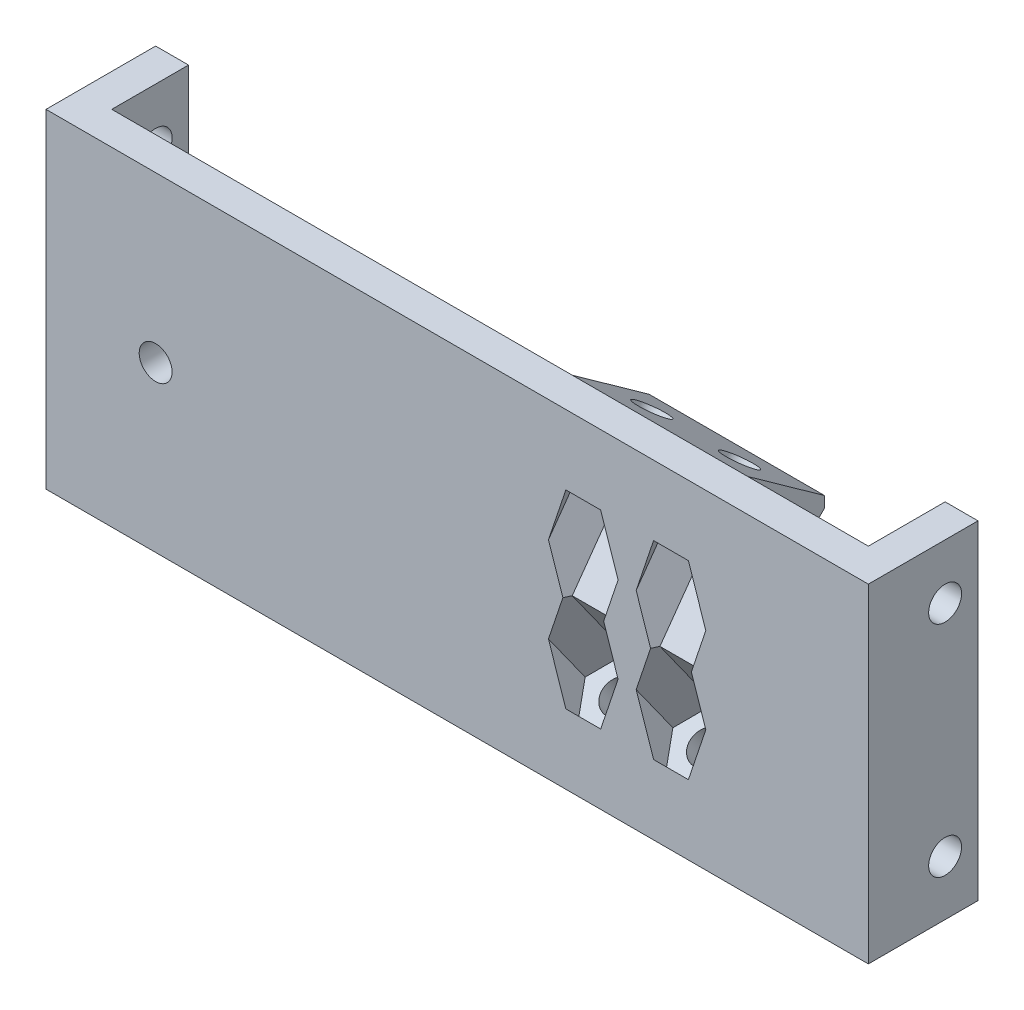
SolidWorks part; units mm, degrees
ref_plane "Front Plane" through (0, 0, 0) normal (0, 0, 1) x (1, 0, 0)
ref_plane "Top Plane" through (0, 0, 0) normal (0, 1, 0) x (1, 0, 0)
ref_plane "Right Plane" through (0, 0, 0) normal (1, 0, 0) x (0, 0, -1)
sketch "Sketch1" plane through (0, 0, 0) normal (0, 0, 1) x (1, 0, 0)
  line L1 (-37.5, -15) -> (37.5, -15)
  line L2 (-37.5, -15) -> (-37.5, 15)
  line L3 (-37.5, 15) -> (37.5, 15)
  line L4 (37.5, -15) -> (37.5, 15)
  line L5 (-37.5, -15) -> (37.5, 15) construction
  line L6 (-37.5, 15) -> (37.5, -15) construction
  point P0 (0, 0)
  dimension "D1" = 30
  dimension "D2" = 75
extrude "Boss-Extrude1" add sketch "Sketch1" along normal blind 3
sketch "Sketch2" plane through (0, 0, 0) normal (0, 0, -1) x (-1, 0, 0)
  line L0 (-37.5, -15) -> (-37.5, 15) construction
  line L1 (-34.5, -15) -> (-37.5, -15)
  line L2 (-34.5, -15) -> (-34.5, 15)
  line L3 (-34.5, 15) -> (-37.5, 15)
  line L4 (-37.5, -15) -> (-37.5, 15)
  line L5 (-34.5, -15) -> (-37.5, 15) construction
  line L6 (-34.5, 15) -> (-37.5, -15) construction
  line L7 (-37.5, 15) -> (37.5, 15) construction
  line L8 (37.5, -15) -> (-37.5, -15) construction
  point P0 (-36, 0)
  dimension "D1" = 0
  dimension "D2" = 0
  dimension "D3" = 3
extrude "Boss-Extrude2" add sketch "Sketch2" along normal blind 7
sketch "Sketch4" plane through (34.5, 0, 0) normal (-1, 0, 0) x (0, 0, 1)
  line L0 (-7, 15) -> (0, 15) construction
  line L1 (-7, -15) -> (-7, 15) construction
  line L2 (0, -15) -> (0, 15) construction
  circle A0 centre (-4, 10) radius 1.5
  dimension "D1" = 3
  dimension "D2" = 5
  dimension "D3" = 3
extrude "Cut-Extrude1" cut sketch "Sketch4" against normal blind 3
mirror "Mirror2" about plane through (0, 0, 0) normal (0, 1, 0) of "Cut-Extrude1"
mirror "Mirror1" about plane through (0, 0, 0) normal (1, 0, 0) of "Mirror2", "Cut-Extrude1", "Boss-Extrude2"
sketch "Sketch5" plane through (0, -15, 0) normal (0, -1, 0) x (1, 0, 0)
  line L0 (-34.5, 0) -> (34.5, 0) construction
  line L1 (7.5, 0) -> (23.5, 0)
  line L2 (7.5, 0) -> (7.5, -7)
  line L3 (7.5, -7) -> (23.5, -7)
  line L4 (23.5, 0) -> (23.5, -7)
  line L5 (34.5, -7) -> (34.5, 0) construction
  dimension "D1" = 16
  dimension "D2" = 11
  dimension "D3" = 0
extrude "Boss-Extrude3" add sketch "Sketch5" against normal blind 8
chamfer "Chamfer1" distance 5 distance2 7 1 edges at (15.5, -15, -7) first distance on face at (15.5, -11, -7)
chamfer "Chamfer2" distance 5 angle 45 1 edges at (15.5, -7, 0)
chamfer "Chamfer3" distance 2 angle 45 1 edges at (15.5, -7, -7)
sketch "Sketch6" plane through (0, -9.9324, -7.0946) normal (0, -0.8137, -0.5812) x (1, 0, 0)
  line L0 (23.5, 8.7186) -> (23.5, 0.1162) construction
  line L1 (7.5, 0.1162) -> (7.5, 8.7186) construction
  line L2 (7.5, 8.7186) -> (23.5, 8.7186) construction
  circle A0 centre (11.5, 4.7186) radius 1.5
  circle A1 centre (19.5, 4.7186) radius 1.5
  dimension "D1" = 3
  dimension "D2" = 3
  dimension "D3" = 4
  dimension "D4" = 4
  dimension "D5" = 4
  dimension "D6" = 4
extrude "Cut-Extrude2" cut sketch "Sketch6" against normal blind 8
sketch "Sketch7" plane through (0, -9.9324, -7.0946) normal (0, -0.8137, -0.5812) x (1, 0, 0)
  line L1 (8.3246, 4.7186) -> (9.9123, 1.9686)
  line L2 (9.9123, 1.9686) -> (13.0877, 1.9686)
  line L3 (13.0877, 1.9686) -> (14.6754, 4.7186)
  line L4 (14.6754, 4.7186) -> (13.0877, 7.4686)
  line L5 (13.0877, 7.4686) -> (9.9123, 7.4686)
  line L6 (9.9123, 7.4686) -> (8.3246, 4.7186)
  line L7 (16.3246, 4.7186) -> (17.9123, 1.9686)
  line L8 (17.9123, 1.9686) -> (21.0877, 1.9686)
  line L9 (21.0877, 1.9686) -> (22.6754, 4.7186)
  line L10 (22.6754, 4.7186) -> (21.0877, 7.4686)
  line L11 (21.0877, 7.4686) -> (17.9123, 7.4686)
  line L12 (17.9123, 7.4686) -> (16.3246, 4.7186)
  circle A0 centre (11.5, 4.7186) radius 2.75 construction
  circle A1 centre (19.5, 4.7186) radius 2.75 construction
  dimension "D1" = 5.5
  dimension "D2" = 5.5
extrude "Cut-Extrude3" cut sketch "Sketch7" against normal through all from offset 5 offset against normal yes
mirror "Mirror3" about plane through (0, 0, 0) normal (0, 1, 0) of "Boss-Extrude3"
chamfer "Chamfer4" distance 7 distance2 5 1 edges at (15.5, 15, -7) first distance on face at (5.1667, 15, -3)
chamfer "Chamfer5" distance 5 angle 45 1 edges at (15.5, 7, 0)
chamfer "Chamfer6" distance 2 angle 45 1 edges at (15.5, 7, -7)
mirror "Mirror4" about plane through (0, 0, 0) normal (0, 1, 0) of "Cut-Extrude3", "Cut-Extrude2"
sketch "Sketch8" plane through (0, 0, 3) normal (0, 0, 1) x (1, 0, 0)
  line L0 (-37.5, 15) -> (-37.5, -15) construction
  circle A0 centre (-27.5, 0) radius 1.5
  dimension "D1" = 3
  dimension "D2" = 10
extrude "Cut-Extrude4" cut sketch "Sketch8" against normal through all
equation "\"D2@Sketch6\"=\"D1@Sketch6\""
equation "\"D4@Sketch6\"=\"D3@Sketch6\""
equation "\"D6@Sketch6\"=\"D5@Sketch6\""
